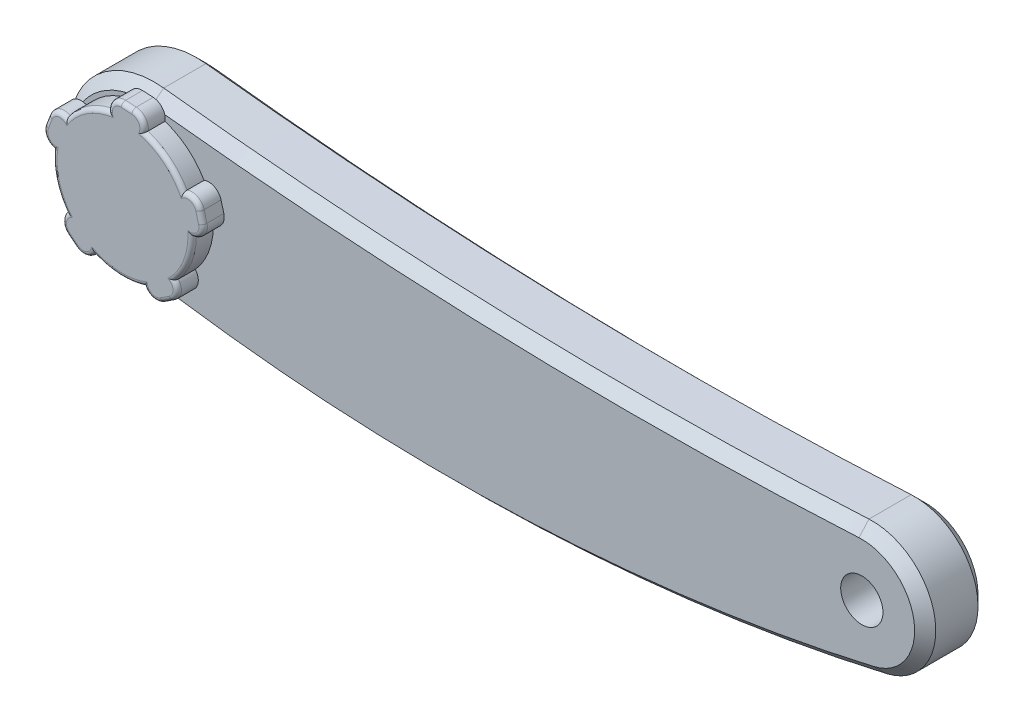
SolidWorks part; units mm, degrees
material "Plain Carbon Steel"
ref_plane "Front Plane" through (0, 0, 0) normal (0, 0, 1) x (1, 0, 0)
ref_plane "Top Plane" through (0, 0, 0) normal (0, 1, 0) x (1, 0, 0)
ref_plane "Right Plane" through (0, 0, 0) normal (1, 0, 0) x (0, 0, -1)
sketch "Sketch1" plane through (0, 0, 0) normal (0, 0, 1) x (1, 0, 0)
  line L0 (-85, 0) -> (85, 0) construction
  arc A0 (-82.7465, 19.8726) -> (-88.3618, -19.7154) centre (-85, 0) ccw
  arc A1 (88.3697, -14.6166) -> (84.1861, 14.9779) centre (85, 0) ccw
  arc A2 (-82.7465, 19.8726) -> (84.1861, 14.9779) centre (29.9265, 1013.5048) ccw
  arc A3 (-88.3618, -19.7154) -> (88.3697, -14.6166) centre (-12.7206, 423.8817) ccw
  point P4 (0, 0)
  point P13 (91.6588, -13.441)
  dimension "D2" = 40
  dimension "D3" = 30
  dimension "D4" = 450
  dimension "D5" = 1000
  dimension "D1" = 170
extrude "Boss-Extrude1" add sketch "Sketch1" along normal mid plane 15
chamfer "Chamfer1" distance 2.5 angle 45 8 edges at (0.2568, -25.9311, -7.5) (99.8523, 2.0996, -7.5) (-104.8018, 2.8087, -7.5) (0.6174, 13.9344, -7.5) (0.2568, -25.9311, 7.5) (99.8523, 2.0996, 7.5) (-104.8018, 2.8087, 7.5) (0.6174, 13.9344, 7.5)
sketch "Sketch2" plane through (0, 0, 7.5) normal (0, 0, 1) x (1, 0, 0)
  circle A0 centre (-85, 0) radius 16.5
  dimension "D1" = 33
extrude "Boss-Extrude2" add sketch "Sketch2" along normal blind 5
sketch "Sketch4" plane through (0, 0, 12.5) normal (0, 0, 1) x (1, 0, 0)
  line L0 (-85, 0) -> (-68.9097, 0)
  line L1 (-66.0119, 3.7765) -> (-66.6676, 6.2235)
  line L2 (-71.0654, 8.0452) -> (-85, 0)
  line L3 (-85, 0) -> (-66.3397, 5) construction
  line L4 (-73.0426, -10.7665) -> (-85, 0)
  line L5 (-85, 0) -> (-80.0278, -15.3028)
  line L6 (-75.5407, -16.8918) -> (-73.416, -15.512)
  line L7 (-91.5445, -14.6992) -> (-85, 0)
  line L8 (-85, 0) -> (-98.0173, -9.4577)
  line L9 (-98.142, -14.2161) -> (-96.1731, -15.8105)
  line L10 (-101.0022, 1.6819) -> (-85, 0)
  line L11 (-85, 0) -> (-98.0173, 9.4577)
  line L12 (-102.5814, 8.1057) -> (-103.4893, 5.7406)
  line L13 (-88.3454, 15.7387) -> (-85, 0)
  line L14 (-85, 0) -> (-80.0278, 15.3028)
  line L15 (-82.724, 19.2257) -> (-85.2539, 19.3583)
  arc A0 (-68.9097, 0) -> (-66.0119, 3.7765) centre (-68.9097, 3) ccw
  arc A1 (-71.0654, 8.0452) -> (-66.6676, 6.2235) centre (-69.5654, 5.4471) cw
  arc A2 (-73.0426, -10.7665) -> (-73.416, -15.512) centre (-75.05, -12.996) cw
  arc A3 (-80.0278, -15.3028) -> (-75.5407, -16.8918) centre (-77.1746, -14.3758) ccw
  arc A4 (-91.5445, -14.6992) -> (-96.1731, -15.8105) centre (-94.2852, -13.479) cw
  arc A5 (-98.0173, -9.4577) -> (-98.142, -14.2161) centre (-96.254, -11.8847) ccw
  arc A6 (-101.0022, 1.6819) -> (-103.4893, 5.7406) centre (-100.6886, 4.6655) cw
  arc A7 (-98.0173, 9.4577) -> (-102.5814, 8.1057) centre (-99.7807, 7.0306) ccw
  arc A8 (-88.3454, 15.7387) -> (-85.2539, 19.3583) centre (-85.4109, 16.3624) cw
  arc A9 (-80.0278, 15.3028) -> (-82.724, 19.2257) centre (-82.881, 16.2299) ccw
  point P10 (-67.6795, 10)
  point P37 (-85, 0)
  circle M22 centre (-85, 0) radius 16.5
  dimension "D3" = 3
  dimension "D1" = 30
  dimension "D2" = 20
  dimension "D4" = 5
extrude "Boss-Extrude3" add sketch "Sketch4" along direction (0, 0, 1) on the side against the normal blind 5 contours A9 L15 A8 M22 | L3 L1 A1 M22 | L3 A0 L1 M22 | A3 L6 A2 M22 | A5 L9 A4 M22 | A7 L12 A6 M22 region at (-68.4431, 6.4563, 12.5) region at (-67.4332, 2.6871, 12.5) region at (-75.3796, -14.8141, 12.5) region at (-96.1162, -13.7273, 12.5) region at (-101.4905, 6.3301, 12.5) region at (-84.0756, 17.6395, 12.5)
fillet "Fillet2" radius 1 20 edges at (-87.5535, 18.4623, 12.5) (-83.9889, 19.292, 12.5) (-80.5307, 18.0943, 12.5) (-74.6162, 12.8229, 12.5) (-68.2303, 8.1337, 12.5) (-66.3397, 5, 12.5) (-66.4102, 1.3409, 12.5) (-69.5959, -5.9131, 12.5) (-72.0823, -13.4355, 12.5) (-74.4784, -16.2019, 12.5) (-77.9802, -17.2656, 12.5) (-85.8635, -16.4774, 12.5) (-93.7861, -16.4372, 12.5) (-97.1575, -15.0133, 12.5) (-99.2513, -12.0116, 12.5) (-100.9378, -4.2705, 12.5) (-103.3478, 3.2767, 12.5) (-103.0354, 6.9231, 12.5) (-100.8276, 9.842, 12.5) (-93.9865, 13.8381, 12.5)
sketch "Sketch5" plane through (0, 0, 7.5) normal (0, 0, 1) x (1, 0, 0)
  circle A0 centre (85, 0) radius 5
  dimension "D1" = 10
extrude "Cut-Extrude1" cut sketch "Sketch5" against normal blind 10
sketch "Sketch6" plane through (0, 0, -7.5) normal (0, 0, -1) x (-1, 0, 0)
  circle A0 centre (85, 0) radius 5
  dimension "D1" = 10
extrude "Boss-Extrude4" add sketch "Sketch6" along normal blind 10
